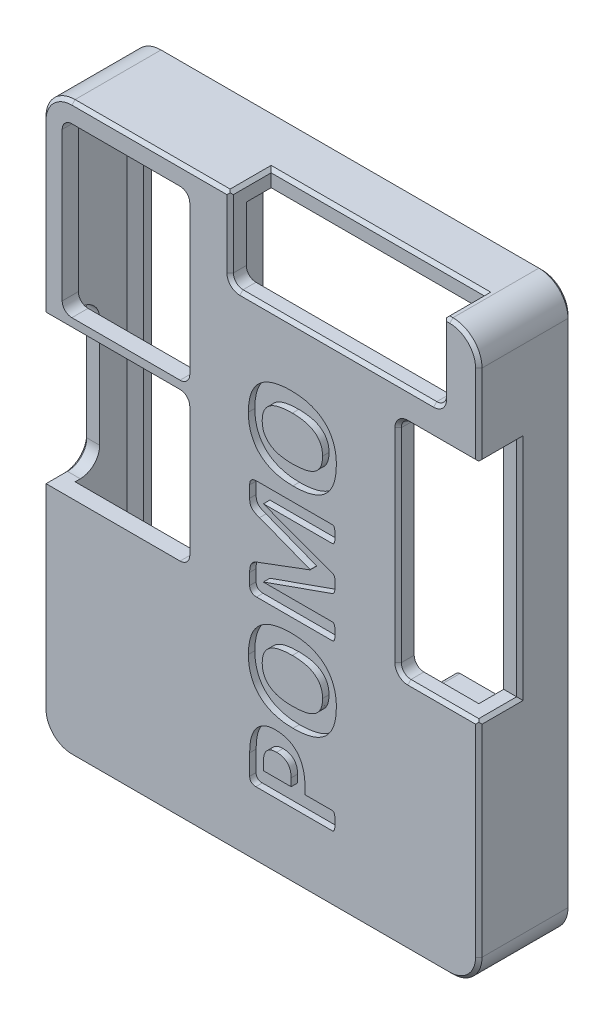
SolidWorks part; units mm, degrees
note: The reader was unsure of these and kept them because the rebuilt part matched: shared geometry of "草图1<3>".
ref_plane "前视基准面" through (0, 0, 0) normal (0, 0, 1) x (1, 0, 0)
ref_plane "上视基准面" through (0, 0, 0) normal (0, 1, 0) x (1, 0, 0)
ref_plane "右视基准面" through (0, 0, 0) normal (1, 0, 0) x (0, 0, -1)
sketch "草图1" plane through (0, 0, 0) normal (0, 0, 1) x (1, 0, 0)
  line L1 (13.5, -17.6) -> (-13.5, -17.6)
  line L2 (13.5, -17.6) -> (13.5, 17.6)
  line L3 (13.5, 17.6) -> (-13.5, 17.6)
  line L4 (-13.5, -17.6) -> (-13.5, 17.6)
  line L5 (13.5, -17.6) -> (-13.5, 17.6) construction
  line L6 (13.5, 17.6) -> (-13.5, -17.6) construction
  line L7 (12.5, -16.6) -> (-12.5, -16.6)
  line L8 (12.5, -16.6) -> (12.5, 16.6)
  line L9 (12.5, 16.6) -> (-12.5, 16.6)
  line L10 (-12.5, -16.6) -> (-12.5, 16.6)
  line L11 (12.5, -16.6) -> (-12.5, 16.6) construction
  line L12 (12.5, 16.6) -> (-12.5, -16.6) construction
  point P0 (0, 0)
  point P6 (0, 0)
  dimension "D1" = 35.2
  dimension "D2" = 27
  dimension "D3" = 25
  dimension "D4" = 33.2
extrude "凸台-拉伸1" add sketch "草图1" against normal blind 2 contours L10 L7 L8 L9 | L4 L1 L2 L3 L7 L10 L9 L8
extrude "凸台-拉伸2" add sketch "草图1<3>" along normal blind 3.72
sketch "草图1<3>" plane through (0, 0, 0) normal (0, 0, 1) x (1, 0, 0) same geometry as "草图1"
fillet "圆角1" radius 1.8 4 edges at (13.5, 17.6, 0.86) (13.5, -17.6, 0.86) (-13.5, -17.6, 0.86) (-13.5, 17.6, 0.86)
fillet "圆角2" radius 0.8 4 edges at (-12.5, -16.6, 0.86) (12.5, -16.6, 0.86) (12.5, 16.6, 0.86) (-12.5, 16.6, 0.86)
sketch "草图2" plane through (-13.5, 0, 0) normal (-1, 0, 0) x (0, 0, 1)
  line L0 (3.72, 15.8) -> (3.72, -15.8) construction
  line L1 (6.24, -3.7) -> (1.2, -3.7)
  line L2 (6.24, -3.7) -> (6.24, 5.5)
  line L3 (6.24, 5.5) -> (1.2, 5.5)
  line L4 (1.2, -3.7) -> (1.2, 5.5)
  line L5 (6.24, -3.7) -> (1.2, 5.5) construction
  line L6 (6.24, 5.5) -> (1.2, -3.7) construction
  line L7 (3.72, -17.6) -> (-2, -17.6) construction
  point P0 (3.72, 0.9)
  dimension "D1" = 13.9
  dimension "D2" = 9.2
  dimension "D3" = 2.52
extrude "切除-拉伸1" cut sketch "草图2" against normal up to next
fillet "圆角3" radius 1.2 2 edges at (-13, -3.7, 1.2) (-13, 5.5, 1.2)
chamfer "倒角1" distance 0.2 angle 45 5 edges at (-13.5, -3.7, 3.06) (-13.5, -3.3485, 1.5515) (-13.5, 0.9, 1.2) (-13.5, 5.5, 3.06) (-13.5, 5.1485, 1.5515)
sketch "草图3" plane through (0, 0, 3.72) normal (0, 0, 1) x (1, 0, 0)
  line L0 (-12.5, 5.5) -> (-12.5, -3.7)
  line L14 (-12.5, -3.7) -> (-13.3, -3.7)
  line L15 (-13.3, -3.7) -> (-13.5, -3.9)
  line L16 (-13.5, -3.9) -> (-13.5, -15.8)
  line L17 (-11.7, -17.6) -> (11.7, -17.6)
  line L18 (13.5, -15.8) -> (13.5, 15.8)
  line L19 (11.7, 17.6) -> (-11.7, 17.6)
  line L20 (-13.5, 15.8) -> (-13.5, 5.7)
  line L21 (-13.5, 5.7) -> (-13.3, 5.5)
  line L22 (-13.3, 5.5) -> (-12.5, 5.5)
  line L23 (-12.5, 5.5) -> (-12.5, 15.8)
  line L24 (-11.7, 16.6) -> (11.7, 16.6)
  line L25 (12.5, 15.8) -> (12.5, -15.8)
  line L26 (11.7, -16.6) -> (-11.7, -16.6)
  line L27 (-12.5, -15.8) -> (-12.5, -3.7)
  line L37 (-12.5, 5.5) -> (-12.5, 15.8)
  line L38 (-11.7, 16.6) -> (11.7, 16.6)
  line L39 (12.5, 15.8) -> (12.5, -15.8)
  line L40 (11.7, -16.6) -> (-11.7, -16.6)
  line L41 (-12.5, -15.8) -> (-12.5, -3.7)
  arc A8 (-13.5, -15.8) -> (-11.7, -17.6) centre (-11.7, -15.8) ccw
  arc A9 (11.7, -17.6) -> (13.5, -15.8) centre (11.7, -15.8) ccw
  arc A10 (13.5, 15.8) -> (11.7, 17.6) centre (11.7, 15.8) ccw
  arc A11 (-11.7, 17.6) -> (-13.5, 15.8) centre (-11.7, 15.8) ccw
  arc A12 (-11.7, 16.6) -> (-12.5, 15.8) centre (-11.7, 15.8) ccw
  arc A13 (12.5, 15.8) -> (11.7, 16.6) centre (11.7, 15.8) ccw
  arc A14 (11.7, -16.6) -> (12.5, -15.8) centre (11.7, -15.8) ccw
  arc A15 (-12.5, -15.8) -> (-11.7, -16.6) centre (-11.7, -15.8) ccw
  arc A20 (-11.7, 16.6) -> (-12.5, 15.8) centre (-11.7, 15.8) ccw
  arc A21 (12.5, 15.8) -> (11.7, 16.6) centre (11.7, 15.8) ccw
  arc A22 (11.7, -16.6) -> (12.5, -15.8) centre (11.7, -15.8) ccw
  arc A23 (-12.5, -15.8) -> (-11.7, -16.6) centre (-11.7, -15.8) ccw
  dimension "D1" = 0
extrude "凸台-拉伸3" add sketch "草图3" against normal blind 1
sketch "草图4" plane through (-12.5, 0, 0) normal (-1, 0, 0) x (0, 0, 1)
  line L4 (2.72, -3.7) -> (3.72, -3.7)
  line L5 (3.72, -3.7) -> (3.72, 5.5)
  line L6 (3.72, 5.5) -> (2.72, 5.5)
  line L7 (2.72, 5.5) -> (2.72, -3.7)
  line L8 (2.72, -3.7) -> (3.72, -3.7)
  line L9 (3.72, -3.7) -> (3.72, 5.5)
  line L10 (3.72, 5.5) -> (2.72, 5.5)
  line L11 (2.72, 5.5) -> (2.72, -3.7)
  dimension "D1" = 0
extrude "切除-拉伸2" cut sketch "草图4" against normal blind 8.1
fillet "圆角4" radius 0.6 2 edges at (-4.4, -3.7, 3.22) (-4.4, 5.5, 3.22)
sketch "草图5" plane through (0, 0, 3.72) normal (0, 0, 1) x (1, 0, 0)
  line L1 (-12.3, 6) -> (-4.4, 6)
  line L4 (-4.4, 6) -> (-4.4, 16.4)
  line L6 (-11.7, 16.4) -> (-5.6, 16.4)
  line L9 (-12.3, 7.2) -> (-12.3, 15.8)
  line L10 (-5.6, 16.4) -> (-4.4, 16.4)
  line L11 (-12.3, 7.2) -> (-12.3, 6)
  line L12 (-13.5, 6) -> (-4.4, 6) construction
  line L13 (-13.5, 6) -> (-13.5, 15.8) construction
  line L14 (-12.3, 7.2) -> (-5.6, 7.2) construction
  line L15 (-5.6, 7.2) -> (-5.6, 16.4) construction
  line L16 (-11.7, 17.6) -> (-4.4, 17.6) construction
  line L17 (-4.4, 6) -> (-4.4, 17.6) construction
  line L18 (11.7, 17.6) -> (-11.7, 17.6) construction
  line L19 (-13.5, 15.8) -> (-13.5, 5.7) construction
  arc A2 (-11.7, 16.4) -> (-12.3, 15.8) centre (-11.7, 15.8) ccw
  arc A3 (-11.7, 17.6) -> (-13.5, 15.8) centre (-11.7, 15.8) ccw construction
  dimension "D1" = 11.6
  dimension "D2" = 9.1
  dimension "D4" = 1.2
  dimension "D3" = 1.2
extrude "切除-拉伸3" cut sketch "草图5" against normal blind 2.54
fillet "圆角5" radius 0.6 3 edges at (-12.3, 6, 3.22) (-4.4, 6, 3.22) (-4.4, 16.4, 3.22)
sketch "草图6" plane through (0, 0, 2.72) normal (0, 0, -1) x (-1, 0, 0)
  line L0 (11.7, -16.6) -> (-11.7, -16.6) construction
  line L1 (5.3, -16.6) -> (3.3, -16.6)
  line L2 (5.3, -16.6) -> (5.3, -13.6)
  line L3 (5.3, -13.6) -> (3.3, -13.6)
  line L4 (3.3, -16.6) -> (3.3, -13.6)
  line L5 (13.5, -3.9) -> (13.5, -15.8) construction
  dimension "D1" = 8.2
  dimension "D2" = 2
  dimension "D3" = 3
extrude "凸台-拉伸4" add sketch "草图6" along normal blind 1.54
fillet "圆角6" radius 0.3 4 edges at (-5.3, -13.6, 1.95) (-5.3, -16.6, 1.95) (-3.3, -16.6, 1.95) (-3.3, -13.6, 1.95)
sketch "草图7" plane through (0, 0, 3.72) normal (0, 0, 1) x (1, 0, 0)
  line L0 (11.7, 17.6) -> (-11.7, 17.6) construction
  line L1 (11.3, 17.6) -> (-1.9, 17.6)
  line L2 (11.3, 17.6) -> (11.3, 12.6)
  line L3 (11.3, 12.6) -> (-1.9, 12.6)
  line L4 (-1.9, 17.6) -> (-1.9, 12.6)
  line L5 (13.5, -15.8) -> (13.5, 15.8) construction
  dimension "D1" = 2.2
  dimension "D2" = 13.2
  dimension "D3" = 5
extrude "切除-拉伸4" cut sketch "草图7" against normal blind 2.54
fillet "圆角7" radius 0.6 2 edges at (11.3, 12.6, 3.22) (-1.9, 12.6, 3.22)
chamfer "倒角2" distance 0.2 angle 45 3 edges at (11.3, 17.6, 2.45) (4.7, 17.6, 1.18) (-1.9, 17.6, 2.45)
sketch "草图8" plane through (0, 0, 3.72) normal (0, 0, 1) x (1, 0, 0)
  line L0 (13.5, -15.8) -> (13.5, 15.8) construction
  line L1 (13.5, 10.7) -> (8.5, 10.7)
  line L2 (13.5, 10.7) -> (13.5, -3.1)
  line L3 (13.5, -3.1) -> (8.5, -3.1)
  line L4 (8.5, 10.7) -> (8.5, -3.1)
  line L5 (-2.1, 17.6) -> (-11.7, 17.6) construction
  dimension "D1" = 6.9
  dimension "D2" = 13.8
  dimension "D3" = 5
extrude "切除-拉伸5" cut sketch "草图8" against normal blind 2.54
fillet "圆角8" radius 0.6 2 edges at (8.5, -3.1, 3.22) (8.5, 10.7, 3.22)
sketch "草图9" plane through (0, 0, 2.72) normal (0, 0, -1) x (-1, 0, 0)
  line L0 (-12.5, -15.8) -> (-12.5, -3.1) construction
  line L1 (-12.5, -3.6) -> (-9.5, -3.6)
  line L2 (-12.5, -3.6) -> (-12.5, -5.1)
  line L3 (-12.5, -5.1) -> (-9.5, -5.1)
  line L4 (-9.5, -3.6) -> (-9.5, -5.1)
  line L6 (11.7, -17.6) -> (-11.7, -17.6) construction
  dimension "D1" = 1.5
  dimension "D2" = 14
  dimension "D3" = 3
extrude "凸台-拉伸5" add sketch "草图9" along normal blind 1.54
fillet "圆角9" radius 0.3 4 edges at (12.5, -5.1, 1.95) (9.5, -5.1, 1.95) (9.5, -3.6, 1.95) (12.5, -3.6, 1.95)
sketch "草图10" plane through (0, 0, 2.72) normal (0, 0, -1) x (-1, 0, 0)
  line L0 (1.9, 16.6) -> (11.7, 16.6) construction
  line L1 (2.4, 16.6) -> (3.9, 16.6)
  line L2 (2.4, 16.6) -> (2.4, 8.6)
  line L3 (2.4, 8.6) -> (3.9, 8.6)
  line L4 (3.9, 16.6) -> (3.9, 8.6)
  line L5 (-13.5, 10.7) -> (-13.5, 15.8) construction
  dimension "D1" = 1.5
  dimension "D2" = 15.9
  dimension "D3" = 8
extrude "凸台-拉伸6" add sketch "草图10" along normal blind 1.54
fillet "圆角10" radius 0.3 4 edges at (-3.9, 8.6, 1.95) (-2.4, 8.6, 1.95) (-3.9, 16.6, 1.95) (-2.4, 16.6, 1.95)
sketch "草图11" plane through (0, 0, 2.72) normal (0, 0, -1) x (-1, 0, 0)
  line L0 (13.5, -3.9) -> (13.5, -15.8) construction
  line L1 (1.5, -2.4) -> (4, -2.4)
  line L2 (1.5, -2.4) -> (1.5, -4.9)
  line L3 (1.5, -4.9) -> (4, -4.9)
  line L4 (4, -2.4) -> (4, -4.9)
  line L5 (2.1, 17.6) -> (11.7, 17.6) construction
  dimension "D1" = 2.5
  dimension "D2" = 2.5
  dimension "D3" = 9.5
  dimension "D4" = 20
extrude "凸台-拉伸7" add sketch "草图11" along normal blind 1.54
fillet "圆角11" radius 0.3 4 edges at (-4, -2.4, 1.95) (-4, -4.9, 1.95) (-1.5, -4.9, 1.95) (-1.5, -2.4, 1.95)
chamfer "倒角3" distance 0.2 angle 45 3 edges at (13.5, -3.1, 2.45) (13.5, 3.8, 1.18) (13.5, 10.7, 2.45)
chamfer "倒角4" distance 0.2 angle 45 10 edges at (-1.9, 15.3, 3.72) (11.3, 15.3, 3.72) (-1.7243, 12.7757, 3.72) (11.1243, 12.7757, 3.72) (4.7, 12.6, 3.72) (11.2, 10.7, 3.72) (11.2, -3.1, 3.72) (8.6757, 10.5243, 3.72) (8.6757, -2.9243, 3.72) (8.5, 3.8, 3.72)
chamfer "倒角5" distance 0.2 angle 45 11 edges at (-6.9, 17.6, 3.72) (-12.9728, 17.0728, 3.72) (-13.5, 10.75, 3.72) (-13.5, -9.85, 3.72) (-12.9728, -17.0728, 3.72) (0, -17.6, 3.72) (12.9728, -17.0728, 3.72) (13.5, -9.55, 3.72) (11.6, 17.6, 3.72) (12.9728, 17.0728, 3.72) (13.5, 13.35, 3.72)
sketch "草图12" plane through (0, 0, 3.72) normal (0, 0, 1) x (1, 0, 0)
  line L0 (4.6, -14) -> (4.6, 17.6) construction
  text T0 "POMO" font "Calibri" height in points 20
extrude "切除-拉伸6" cut sketch "草图12" against normal blind 0.4
chamfer "倒角6" distance 0.2 angle 45 8 edges at (12.9728, 17.0728, -2) (13.5, 0, -2) (0, 17.6, -2) (12.9728, -17.0728, -2) (-12.9728, 17.0728, -2) (0, -17.6, -2) (-13.5, 0, -2) (-12.9728, -17.0728, -2)
ref_plane "基准面1" through (0, 0, -1) normal (0, 0, -1) x (-1, 0, 0)
sketch "草图13" plane through (0, 0, -1) normal (0, 0, -1) x (-1, 0, 0)
  line L0 (-11.7, 16.6) -> (11.7, 16.6) construction
  line L2 (-12.5, -15.8) -> (-12.5, 15.8) construction
  line L3 (12.5, -15.8) -> (12.5, 15.8) construction
  line L4 (-11.7, -16.6) -> (11.7, -16.6) construction
  line L5 (12.5, -15.8) -> (12.5, 15.8)
  line L6 (-11.7, -16.6) -> (11.7, -16.6)
  line L7 (-12.5, -15.8) -> (-12.5, 15.8)
  line L8 (-11.7, 16.6) -> (11.7, 16.6)
  arc A0 (-11.7, 16.6) -> (-12.5, 15.8) centre (-11.7, 15.8) ccw construction
  arc A1 (-12.5, -15.8) -> (-11.7, -16.6) centre (-11.7, -15.8) ccw construction
  arc A2 (12.5, 15.8) -> (11.7, 16.6) centre (11.7, 15.8) ccw construction
  arc A3 (11.7, -16.6) -> (12.5, -15.8) centre (11.7, -15.8) ccw construction
  arc A4 (12.5, 15.8) -> (11.7, 16.6) centre (11.7, 15.8) ccw
  arc A5 (11.7, -16.6) -> (12.5, -15.8) centre (11.7, -15.8) ccw
  arc A6 (-12.5, -15.8) -> (-11.7, -16.6) centre (-11.7, -15.8) ccw
  arc A7 (-11.7, 16.6) -> (-12.5, 15.8) centre (-11.7, 15.8) ccw
ref_plane "基准面2" through (-3.5, 0, 0) normal (-1, 0, 0) x (0, 0, 1)
sketch "草图14" plane through (-3.5, 0, 0) normal (-1, 0, 0) x (0, 0, 1)
  line L0 (-1.5, 16.6) -> (-0.5, 16.6)
  line L1 (-2, 16.6) -> (2.72, 16.6) construction
  line L2 (-1.5, 16.6) -> (-1, 17.1)
  line L3 (-1, 17.1) -> (-0.5, 16.6)
  line L4 (-2, 17.4) -> (-2, 15.8) construction
  dimension "D1" = 0.5
  dimension "D2" = 1
  dimension "D3" = 45
  dimension "D4" = 90
sweep "切除-扫描1" cut profiles "草图14" path "草图13"
